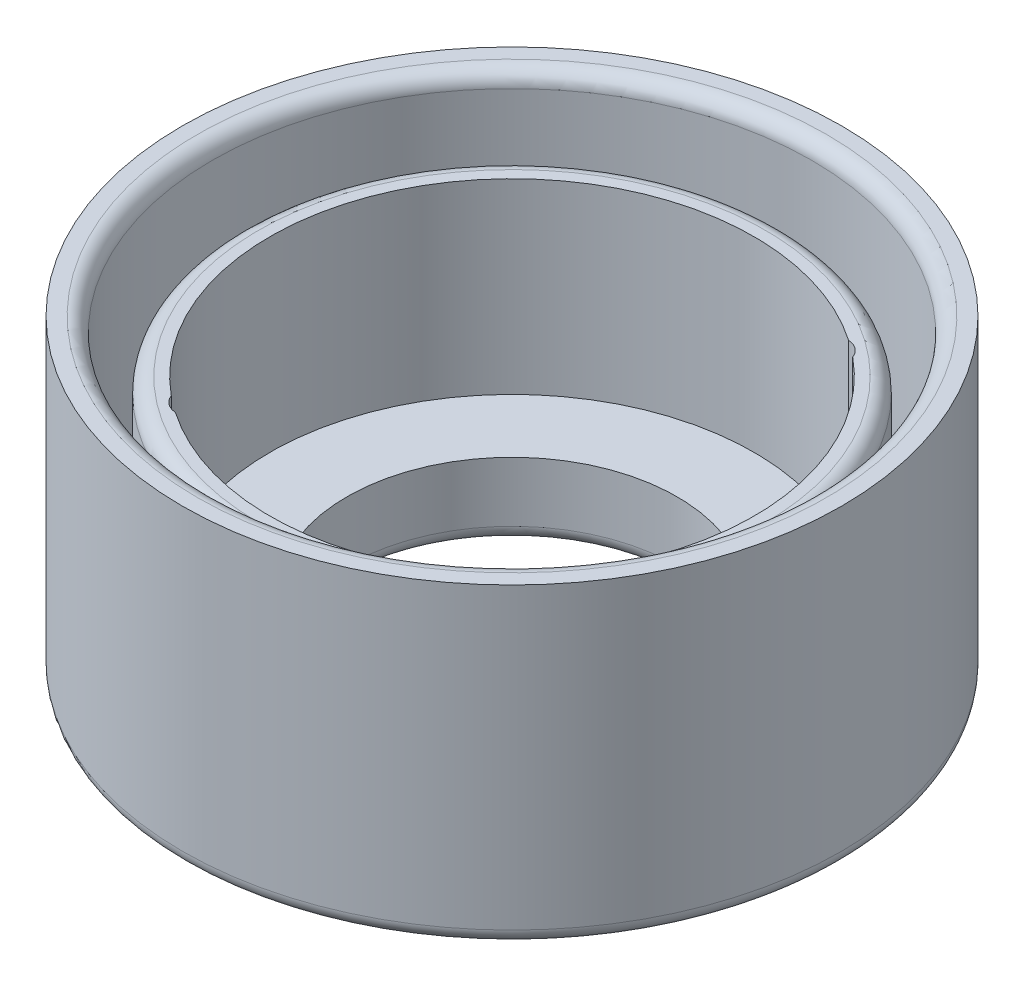
SolidWorks part; units mm, degrees
ref_plane "Alzado" through (0, 0, 0) normal (0, 0, 1) x (1, 0, 0)
ref_plane "Planta" through (0, 0, 0) normal (0, 1, 0) x (1, 0, 0)
ref_plane "Vista lateral" through (0, 0, 0) normal (1, 0, 0) x (0, 0, -1)
sketch "Croquis1" plane through (0, 0, 0) normal (0, 1, 0) x (1, 0, 0)
  circle A0 centre (0, 0) radius 17.95
  circle A1 centre (0, 0) radius 20.05
  circle A2 centre (0, 0) radius 22.05
  circle A3 centre (0, 0) radius 16.2
  dimension "D1" = 35.9
  dimension "D2" = 1.75
  dimension "D3" = 40.1
  dimension "D4" = 2
extrude "Saliente-Extruir1" add sketch "Croquis1" along normal blind 16 contours A2 A1 region at (-21.4263, 0, 0)
extrude "Saliente-Extruir2" add sketch "Croquis1<4>" along normal blind 12.5 separate body contours A0 A3 region at (-17.4423, 0, 0)
sketch "Croquis1<4>" plane through (0, 0, 0) normal (0, 1, 0) x (1, 0, 0) same geometry as "Croquis1"
extrude "Saliente-Extruir4" add sketch "Croquis1<6>" against normal blind 5 contours A3 | A0 A3 | A1 A0 | A2 A1 region at (-17.4423, 0, 0) region at (-19.4829, 0, 0) region at (-21.4263, 0, 0) region at (0, 0, 0)
sketch "Croquis1<6>" plane through (0, 0, 0) normal (0, 1, 0) x (1, 0, 0) same geometry as "Croquis1"
sketch "Croquis4" plane through (0, -5, 0) normal (0, -1, 0) x (1, 0, 0)
  line L0 (-9.1, 12.1) -> (0, 0) construction
  line L1 (0, 0) -> (9.1, -12.1) construction
  line L3 (13, 16) -> (-13, 16) construction
  line L4 (13, 16) -> (13, -16) construction
  line L5 (13, -16) -> (-13, -16) construction
  line L6 (-13, 16) -> (-13, -16) construction
  line L7 (13, 16) -> (-13, -16) construction
  line L8 (13, -16) -> (-13, 16) construction
  circle A0 centre (0, 0) radius 11.05
  circle A1 centre (-9.1, 12.1) radius 1.25
  circle A2 centre (9.1, -12.1) radius 1.25
  point P11 (-9.1, 13.35)
  point P12 (-10.35, 12.1)
  dimension "D1" = 22.1
  dimension "D4" = 2.5
  dimension "D2" = 26
  dimension "D3" = 32
  dimension "D5" = 2.65
  dimension "D6" = 2.65
extrude "Cortar-Extruir1" cut sketch "Croquis4" against normal up to next
sketch "Croquis5" plane through (0, -5, 0) normal (0, -1, 0) x (1, 0, 0)
  circle A0 centre (-9.1, 12.1) radius 1.25 construction
  circle A1 centre (9.1, -12.1) radius 1.25 construction
  circle A2 centre (-9.1, 12.1) radius 1.25
  circle A3 centre (9.1, -12.1) radius 1.25
  circle A4 centre (-9.1, 12.1) radius 2.5
  circle A5 centre (9.1, -12.1) radius 2.5
  dimension "D1" = 5
extrude "Cortar-Extruir2" cut sketch "Croquis5" against normal blind 3
fillet "Redondeo1" radius 1 1 edges at (0, -5, -11.05)
fillet "Redondeo2" radius 1 2 edges at (0, 12.5, 17.95) (0, 16, 20.05)
fillet "Redondeo3" radius 1 1 edges at (0, -5, 22.05)
